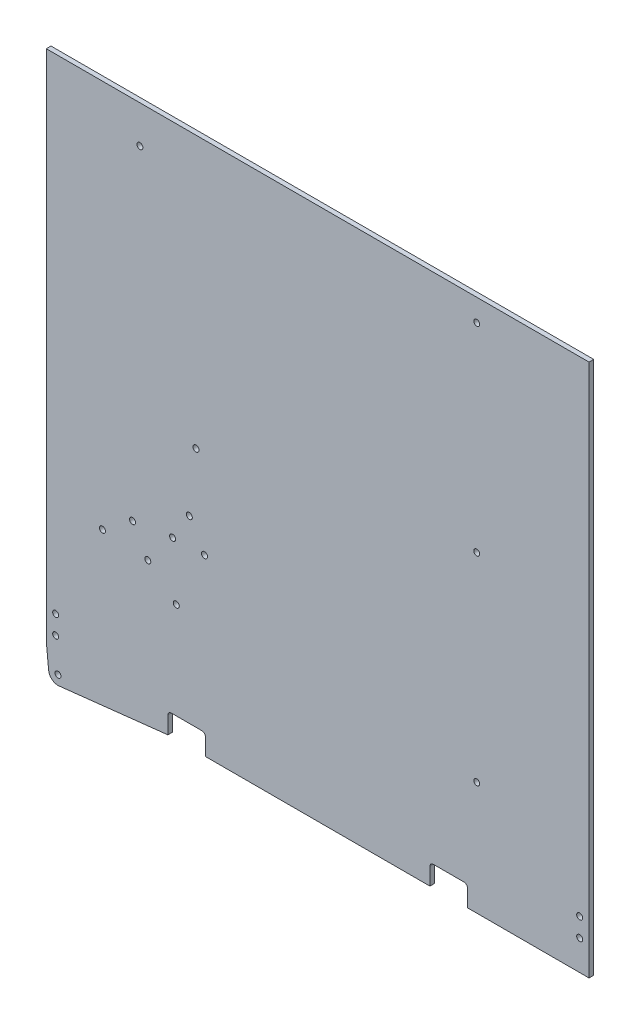
SolidWorks part; units mm, degrees
ref_plane "Front Plane" through (0, 0, 0) normal (0, 0, 1) x (1, 0, 0)
ref_plane "Top Plane" through (0, 0, 0) normal (0, 1, 0) x (1, 0, 0)
ref_plane "Right Plane" through (0, 0, 0) normal (1, 0, 0) x (0, 0, -1)
sketch "Sketch1" plane through (0, 0, 0) normal (0, 0, 1) x (1, 0, 0)
  line L0 (82.55, -20.32) -> (82.55, -6.35)
  line L2 (0, 0) -> (0, 341.63)
  line L3 (0, 341.63) -> (368.3, 341.63)
  line L4 (368.3, -20.32) -> (368.3, 341.63)
  line L5 (82.55, -6.35) -> (107.95, -6.35)
  line L6 (107.95, -6.35) -> (107.95, -20.32)
  line L7 (107.95, -20.32) -> (260.35, -20.32)
  line L8 (260.35, -20.32) -> (260.35, -6.35)
  line L9 (260.35, -6.35) -> (285.75, -6.35)
  line L10 (285.75, -6.35) -> (285.75, -20.32)
  line L11 (285.75, -20.32) -> (368.3, -20.32)
  line L12 (361.95, 12.7) -> (368.3, 12.7) construction
  line L13 (0, 0) -> (6.35, 0) construction
  line L14 (0.0315, -6.9818) -> (1.619, -22.8568)
  line L15 (8.6391, -28.5361) -> (82.55, -20.32)
  line L16 (0, 0) -> (0, -6.35)
  line L17 (85.725, 97.155) -> (82.9754, 95.5675) construction
  line L18 (97.0634, 115.6163) -> (58.5686, 93.3913) construction
  line L19 (97.0634, 115.6163) -> (107.3822, 97.7437) construction
  line L20 (58.5686, 93.3913) -> (68.8873, 75.5187) construction
  line L21 (107.3822, 97.7437) -> (68.8873, 75.5187) construction
  line L22 (97.0634, 115.6163) -> (68.8873, 75.5187) construction
  line L23 (58.5686, 93.3913) -> (107.3822, 97.7437) construction
  line L24 (7.9375, -22.225) -> (88.2169, 59.1366) construction
  line L25 (292.1, 56.63) -> (292.1, 191.63) construction
  line L26 (292.1, 191.63) -> (292.1, 326.63) construction
  circle A0 centre (6.35, 0) radius 2.032
  circle A1 centre (6.35, 12.7) radius 2.032
  circle A2 centre (361.95, 0) radius 2.032
  circle A3 centre (361.95, 12.7) radius 2.032
  arc A5 (1.619, -22.8568) -> (8.6391, -28.5361) centre (7.9375, -22.225) ccw
  circle A6 centre (7.9375, -22.225) radius 2.032
  arc A7 (0, -6.35) -> (0.0315, -6.9818) centre (6.35, -6.35) ccw
  circle A8 centre (38.1, 78.105) radius 2.032
  circle A9 centre (85.725, 97.155) radius 2.032
  circle A10 centre (58.5686, 93.3913) radius 2.032
  circle A11 centre (68.8873, 75.5187) radius 2.032
  circle A12 centre (107.3822, 97.7437) radius 2.032
  circle A13 centre (97.0634, 115.6163) radius 2.032
  circle A14 centre (88.2169, 59.1366) radius 2.032
  circle A15 centre (292.1, 56.63) radius 2
  circle A16 centre (292.1, 191.63) radius 2
  circle A17 centre (292.1, 326.63) radius 2
  circle A18 centre (63.5, 316.23) radius 2.032
  circle A19 centre (101.6, 157.48) radius 2.032
  point P54 (99.4428, 223.4817)
  dimension "D6" = 4.064
  dimension "D10" = 6.35
  dimension "D11" = 4.064
  dimension "D17" = 38.1
  dimension "D27" = 4
  dimension "D31" = 4.064
  dimension "D32" = 25.4
  dimension "D2" = 361.95
  dimension "D3" = 13.97
  dimension "D4" = 25.4
  dimension "D5" = 152.4
  dimension "D7" = 12.7
  dimension "D8" = 6.35
  dimension "D9" = 20.32
  dimension "D12" = 22.225
  dimension "D13" = 1.5875
  dimension "D14" = 82.55
  dimension "D15" = 368.3
  dimension "D16" = 6.35
  dimension "D18" = 98.425
  dimension "D19" = 47.625
  dimension "D20" = 19.05
  dimension "D21" = 3.175
  dimension "D22" = 60
  dimension "D23" = 20.6375
  dimension "D24" = 44.45
  dimension "D25" = 38.1
  dimension "D26" = 114.3
  dimension "D28" = 135
  dimension "D29" = 15
  dimension "D30" = 76.2
  dimension "D33" = 63.5
  dimension "D34" = 184.15
  dimension "D35" = 101.6
extrude "Boss-Extrude1" add sketch "Sketch1" along normal blind 3.175
fillet "Fillet1" radius 2.286 4 edges at (285.75, -6.35, 1.5875) (107.95, -6.35, 1.5875) (260.35, -6.35, 1.5875) (82.55, -6.35, 1.5875)
